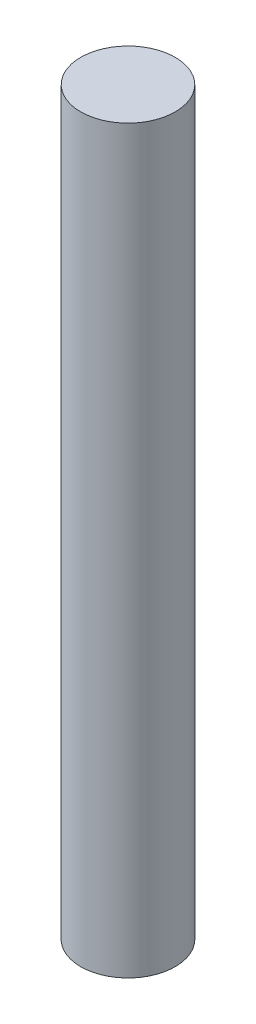
SolidWorks part; units mm, degrees
ref_plane "Front Plane" through (0, 0, 0) normal (0, 0, 1) x (1, 0, 0)
ref_plane "Top Plane" through (0, 0, 0) normal (0, 1, 0) x (1, 0, 0)
ref_plane "Right Plane" through (0, 0, 0) normal (1, 0, 0) x (0, 0, -1)
sketch "Sketch1" plane through (0, 0, 0) normal (0, 1, 0) x (1, 0, 0)
  circle A0 centre (0, 0) radius 3
  dimension "D1" = 6
extrude "Boss-Extrude1" add sketch "Sketch1" along normal blind 47
